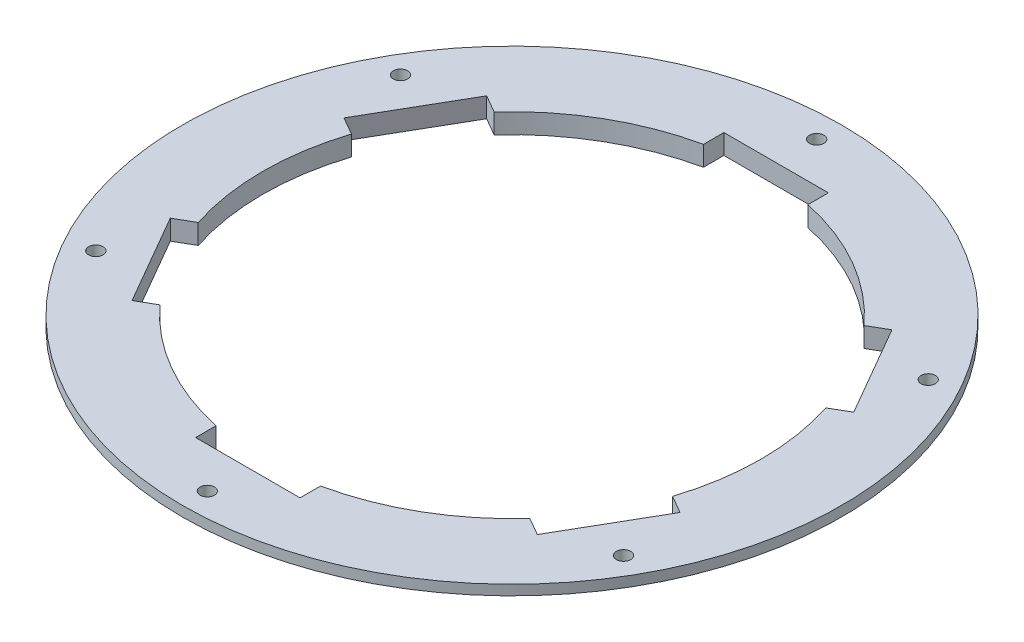
SolidWorks part; units mm, degrees
material "6061 Alloy"
ref_plane "Front Plane" through (0, 0, 0) normal (0, 0, 1) x (1, 0, 0)
ref_plane "Top Plane" through (0, 0, 0) normal (0, 1, 0) x (1, 0, 0)
ref_plane "Right Plane" through (0, 0, 0) normal (1, 0, 0) x (0, 0, -1)
sketch "Sketch1" plane through (0, 0, 0) normal (0, 1, 0) x (1, 0, 0)
  line L0 (-13.335, -62.2139) -> (-13.335, -66.1054)
  line L1 (13.335, -62.2139) -> (13.335, -66.1054)
  line L2 (-13.335, -67.437) -> (13.335, -67.437)
  line L3 (13.335, -66.1054) -> (13.335, -67.437)
  line L4 (-13.335, -66.1054) -> (-13.335, -67.437)
  circle A0 centre (0, 0) radius 63.627
  circle A1 centre (0, 0) radius 84.1375
  circle A2 centre (0, 0) radius 67.437
  circle A3 centre (0, -77.7875) radius 1.8288
  dimension "D1" = 127.254
  dimension "D2" = 168.275
  dimension "D8" = 3.6576
  dimension "D4" = 13.335
  dimension "D5" = 13.335
  dimension "D7" = 77.7875
  dimension "D3" = 3.81
extrude "Boss-Extrude1" add sketch "Sketch1" along normal blind 5.08 contours L1 A2 L0 A0 | A1 A2 A0 region at (-15.233, 0, 64.1597) region at (-81.7577, 0, 0)
pattern_circular "CirPattern1" count 6 over 360 about axis through (0, 5.08, 0) along (0, 1, 0) of face at (-13.335, 2.54, 64.8255) of face at (13.335, 2.54, 64.8255) of face at (0, 5.08, 79.6163) of face at (0, 2.54, 67.437)
sketch "Sketch2" plane through (0, 0, 0) normal (1, 0, 0) x (0, 0, -1)
  line L0 (84.1375, 5.08) -> (-84.1375, 5.08) construction
  line L1 (-84.1375, 0) -> (84.1375, 0) construction
  line L2 (84.1375, 5.08) -> (-84.1375, 5.08)
  line L3 (-84.1375, 0) -> (84.1375, 0)
  line L4 (0, 0) -> (0, 5.08) construction
  circle A0 centre (-83.2231, 0) radius 2.667
  dimension "D1" = 5.334
  dimension "D2" = 0.9144
revolve "Cut-Revolve1" cut sketch "Sketch2" angle 360 about L4 region at (0, 0, 85.8147)
sketch "Sketch4" plane through (0, 0, 0) normal (0, -1, 0) x (1, 0, 0)
  line L0 (0, 0) -> (35.4013, -61.3168) construction
  line L1 (0, 0) -> (0, -39.7137) construction
  circle A0 centre (35.4013, -61.3168) radius 5.588
  circle M34 centre (0, 0) radius 80.5561
  dimension "D2" = 11.176
  dimension "D1" = 70.8025
  dimension "D3" = 30
extrude "Cut-Extrude1" cut sketch "Sketch4" against normal blind 1.905 contours A0 M34 region at (35.4013, 0, -61.3168)
pattern_circular "CirPattern2" count 3 over 360 about axis through (0, 0, 0) along (0, 1, 0) of "Cut-Extrude1"
equation "\"Middle Coupler Inner Daimeter\"= 4.5in"
equation "\"Middle Coupler  Wall Thickness\" = 0.25in"
equation "\"Middle Coupler Bottom Thickness\"= 0.2in"
equation "\"Bearing Rail Offset\"= 0.45in"
equation "\"3-56 UNF Tap\"= 0.089in"
equation "\"3-56 UNF Clearance\"= 0.104in"
equation "\"Ball Bearing Distance\"= 0.03in"
equation "\"D1@Sketch1\"=\"Middle Coupler Inner Daimeter\"+0.5+0.005*2in"
equation "\"TCA Outer Diameter\" = 6.625in"
equation "\"D2@Sketch1\"=\"TCA Outer Diameter\""
equation "\"D4@Sketch1\"=0.50 + (0.05/2)"
equation "\"D5@Sketch1\"=\"D4@Sketch1\""
equation "\"D7@Sketch1\"=(\"D2@Sketch1\"-0.5)/2"
equation "\"D8@Sketch1\"=\"6-32 Clearance\""
equation "\"D2@Sketch2\"=\"Interstage Aeroframe Wall Thickness\"/2"
equation "\"Interstage Aeroframe Wall Thickness\" = 0.072in"
equation "\"D1@Sketch4\"=((\"Middle Coupler Inner Daimeter\"+0.625in)/2in+0.225in)"
equation "\"Compression Spring OD\"= 0.42in"
equation "\"10-24 Tap\"= 0.157in"
equation "\"10-24 Clearance\"= 0.196in"
equation "\"D2@Sketch4\"=\"Compression Spring OD\"+0.02"
equation "\"D3@Sketch1\"=0.125in+(0.05/2)"
equation "\"Lower Stage Fuselage Wall Thickness\" = 0.25in"
equation "\"6-32 Tap\" = 0.107in"
equation "\"1/4-20 Tap\" = 0.201in"
equation "\"3-48 Tap\"= 0.079in"
equation "\"12-24 Tap\" = 0.177in"
equation "\"3-48 Clearance\" = 0.104in"
equation "\"6-32 Clearance\" = 0.144"
